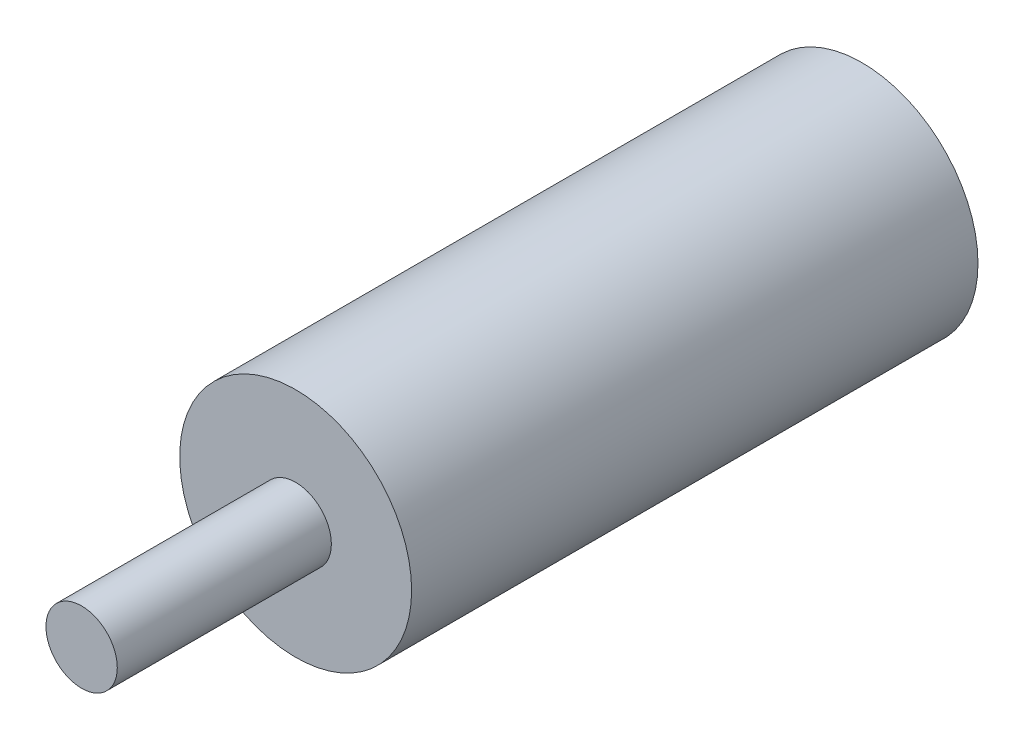
SolidWorks part; units mm, degrees
ref_plane "Front Plane" through (0, 0, 0) normal (0, 0, 1) x (1, 0, 0)
ref_plane "Top Plane" through (0, 0, 0) normal (0, 1, 0) x (1, 0, 0)
ref_plane "Right Plane" through (0, 0, 0) normal (1, 0, 0) x (0, 0, -1)
ref_plane "Plane1"
sketch "Sketch1" plane through (0, 0, 0) normal (0, 0, 1) x (1, 0, 0)
  circle A0 centre (0, 0) radius 26
  circle A1 centre (0, 0) radius 8
  dimension "D1" = 52
  dimension "D2" = 16
extrude "Extrusion1" add sketch "Sketch1" along normal blind 127 contours A0 A1 region at (-25.2646, 0, 0)
ref_plane "Plane2"
sketch "Sketch2" plane through (0, 0, 0) normal (0, 0, 1) x (1, 0, 0)
  circle A0 centre (0, 0) radius 8
  dimension "D1" = 16
extrude "Extrusion2" add sketch "Sketch2" along normal blind 175
